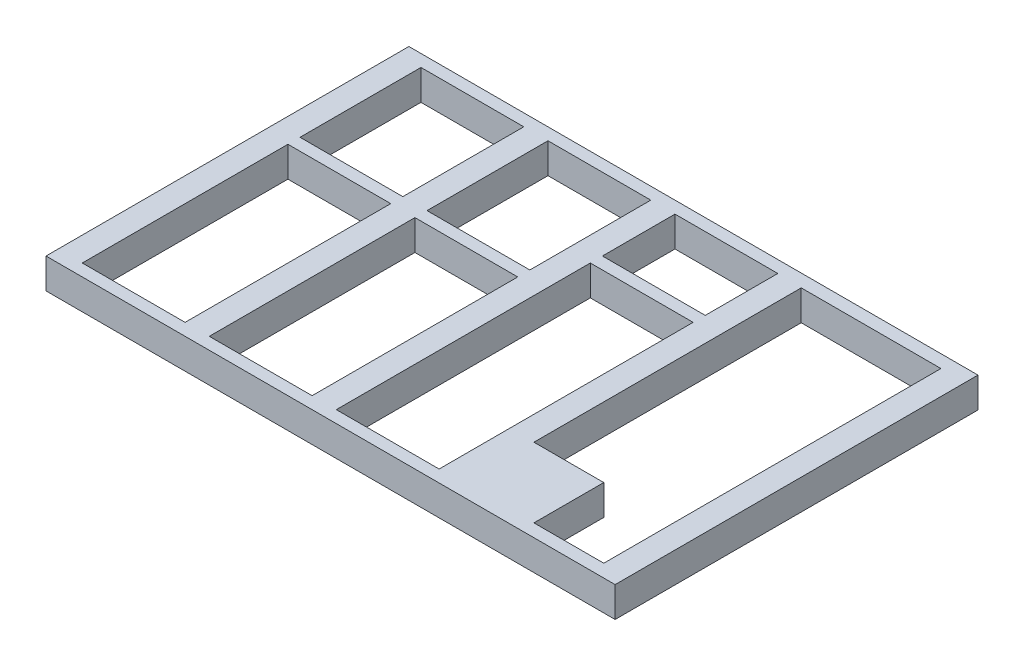
SolidWorks part; units mm, degrees
ref_plane "Front" through (0, 0, 0) normal (0, 0, 1) x (1, 0, 0)
ref_plane "Top" through (0, 0, 0) normal (0, 1, 0) x (1, 0, 0)
ref_plane "Right" through (0, 0, 0) normal (1, 0, 0) x (0, 0, -1)
sketch "Sketch1" plane through (0, 0, 0) normal (0, 1, 0) x (1, 0, 0)
  line L0 (19.95, 27.875) -> (43.05, 27.875)
  line L1 (-47.05, -30) -> (47.05, -30)
  line L2 (-47.05, -30) -> (-47.05, 30)
  line L3 (-47.05, 30) -> (47.05, 30)
  line L4 (47.05, -30) -> (47.05, 30)
  line L5 (-47.05, -30) -> (47.05, 30) construction
  line L6 (-47.05, 30) -> (47.05, -30) construction
  line L7 (-43.05, -28) -> (-26.05, -28)
  line L8 (-43.05, -28) -> (-43.05, 6)
  line L9 (-43.05, 6) -> (-26.05, 6)
  line L10 (-26.05, -28) -> (-26.05, 6)
  line L11 (-43.05, -28) -> (-26.05, 6) construction
  line L12 (-43.05, 6) -> (-26.05, -28) construction
  line L13 (-43.05, 8) -> (-26.05, 8)
  line L14 (-43.05, 8) -> (-43.05, 28)
  line L15 (-43.05, 28) -> (-26.05, 28)
  line L16 (-26.05, 8) -> (-26.05, 28)
  line L17 (-43.05, 8) -> (-26.05, 28) construction
  line L18 (-43.05, 28) -> (-26.05, 8) construction
  line L19 (-5.05, -28) -> (-22.05, -28)
  line L20 (-5.05, -28) -> (-5.05, 6)
  line L21 (-5.05, 6) -> (-22.05, 6)
  line L22 (-22.05, -28) -> (-22.05, 6)
  line L23 (-5.05, -28) -> (-22.05, 6) construction
  line L24 (-5.05, 6) -> (-22.05, -28) construction
  line L25 (-5.05, 28) -> (-22.05, 28)
  line L26 (-5.05, 28) -> (-5.05, 8)
  line L27 (-5.05, 8) -> (-22.05, 8)
  line L28 (-22.05, 28) -> (-22.05, 8)
  line L29 (-5.05, 28) -> (-22.05, 8) construction
  line L30 (-5.05, 8) -> (-22.05, 28) construction
  line L31 (-1.05, -28) -> (15.95, -28)
  line L32 (-1.05, -28) -> (-1.05, 14)
  line L33 (-1.05, 14) -> (15.95, 14)
  line L34 (15.95, -28) -> (15.95, 14)
  line L35 (-1.05, -28) -> (15.95, 14) construction
  line L36 (-1.05, 14) -> (15.95, -28) construction
  line L37 (-1.05, 16) -> (15.95, 16)
  line L38 (-1.05, 16) -> (-1.05, 28)
  line L39 (-1.05, 28) -> (15.95, 28)
  line L40 (15.95, 16) -> (15.95, 28)
  line L41 (-1.05, 16) -> (15.95, 28) construction
  line L42 (-1.05, 28) -> (15.95, 16) construction
  line L43 (43.05, 27.875) -> (43.05, -27.875)
  line L44 (43.05, -27.875) -> (31.5, -27.875)
  line L45 (31.5, -27.875) -> (31.5, -16.325)
  line L46 (31.5, -16.325) -> (19.95, -16.325)
  line L47 (19.95, -16.325) -> (19.95, 27.875)
  point P0 (0, 0)
  point P6 (-34.55, -11)
  point P11 (-34.55, 18)
  point P16 (-13.55, -11)
  point P21 (-13.55, 18)
  point P26 (7.45, -7)
  point P31 (7.45, 22)
  dimension "D1" = 94.1
  dimension "D2" = 60
  dimension "D3" = 4
  dimension "D4" = 2
  dimension "D5" = 17
  dimension "D6" = 4
  dimension "D7" = 17
  dimension "D8" = 2
  dimension "D9" = 4
  dimension "D10" = 2
  dimension "D11" = 17
  dimension "D12" = 4
  dimension "D13" = 17
  dimension "D14" = 4
  dimension "D15" = 17
  dimension "D16" = 4
  dimension "D17" = 17
  dimension "D18" = 2
  dimension "D19" = 2
  dimension "D20" = 34
  dimension "D21" = 20
  dimension "D22" = 20
  dimension "D23" = 34
  dimension "D24" = 42
  dimension "D25" = 12
  dimension "D26" = 2.125
  dimension "D27" = 2.125
  dimension "D28" = 4
  dimension "D29" = 4
  dimension "D30" = 11.55
  dimension "D31" = 11.55
extrude "Boss-Extrude1" add sketch "Sketch1" along normal blind 5
